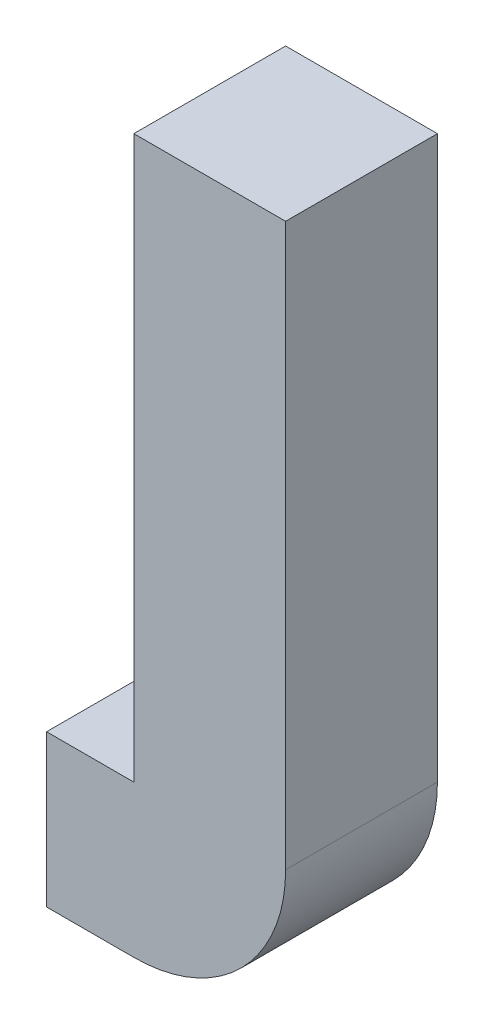
SolidWorks part; units mm, degrees
ref_plane "Front Plane" through (0, 0, 0) normal (0, 0, 1) x (1, 0, 0)
ref_plane "Top Plane" through (0, 0, 0) normal (0, 1, 0) x (1, 0, 0)
ref_plane "Right Plane" through (0, 0, 0) normal (1, 0, 0) x (0, 0, -1)
sketch "Sketch1" plane through (0, 0, 0) normal (1, 0, 0) x (0, 0, -1)
  line L0 (3.175, 34.925) -> (34.925, 34.925)
  line L1 (0, 0) -> (38.1, 0)
  line L2 (0, 0) -> (0, 38.1)
  line L3 (0, 38.1) -> (38.1, 38.1)
  line L4 (38.1, 0) -> (38.1, 38.1)
  line L5 (34.925, 3.175) -> (34.925, 34.925)
  line L6 (3.175, 3.175) -> (34.925, 3.175)
  line L7 (3.175, 3.175) -> (3.175, 34.925)
  dimension "D1" = 38.1
  dimension "D2" = 3.175
sketch "Sketch2" plane through (0, 0, 0) normal (0, 0, 1) x (1, 0, 0)
  line L0 (60, 102.7914) -> (60, -42.6305) construction
  line L1 (0, 3.175) -> (0, 34.925) construction
  line L2 (40.95, 179.05) -> (40.95, 38.1)
  line L3 (0, 19.05) -> (21.9, 19.05)
  arc A0 (40.95, 38.1) -> (21.9, 19.05) centre (21.9, 38.1) cw
  dimension "D3" = 19.05
  dimension "D1" = 60
  dimension "D2" = 19.05
  dimension "D4" = 160
sweep "Sweep1" add profiles "Sketch1" path "Sketch2"
ref_plane "Plane1" through (0, 0, -19.05) normal (0, 0, -1) x (-1, 0, 0)
ref_plane "Plane2" through (40.95, 0, 0) normal (1, 0, 0) x (0, 0, -1)
ref_axis "Axis1" through (40.95, 31.0525, -19.05) along (0, 1, 0)
sketch "Sketch3" plane through (0, 179.05, 0) normal (0, 1, 0) x (1, 0, 0)
  line L5 (25.075, 3.175) -> (56.825, 3.175)
  line L6 (25.075, 34.925) -> (25.075, 3.175)
  line L7 (56.825, 34.925) -> (25.075, 34.925)
  line L8 (56.825, 3.175) -> (56.825, 34.925)
  line L9 (25.075, 3.175) -> (56.825, 3.175)
  line L10 (25.075, 34.925) -> (25.075, 3.175)
  line L11 (56.825, 34.925) -> (25.075, 34.925)
  line L12 (56.825, 3.175) -> (56.825, 34.925)
  dimension "D1" = 0
sweep "Sweep2" add profiles "Sketch3" path "Sketch2<2>"
sketch "Sketch2<2>" plane through (0, 0, 0) normal (0, 0, 1) x (1, 0, 0) same geometry as "Sketch2"
ref_point "Point1"
ref_axis "Axis2" through (0, 19.05, -19.05) along (-1, 0, 0)
